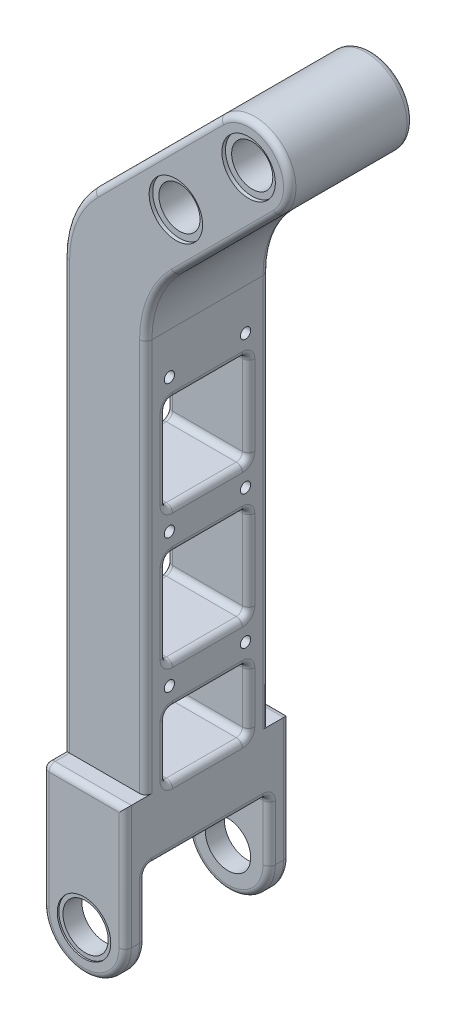
SolidWorks part; units mm, degrees
material "6061 合金"
ref_plane "前视基准面" through (0, 0, 0) normal (0, 0, 1) x (1, 0, 0)
ref_plane "上视基准面" through (0, 0, 0) normal (0, 1, 0) x (1, 0, 0)
ref_plane "右视基准面" through (0, 0, 0) normal (1, 0, 0) x (0, 0, -1)
other "Configuration Table"
sketch "草图1" plane through (0, 0, 0) normal (0, 0, 1) x (1, 0, 0)
  circle A0 centre (0, 0) radius 20
  circle A1 centre (0, 0) radius 10
  dimension "D1" = 40
  dimension "D2" = 20
extrude "凸台-拉伸1" add sketch "草图1" along normal blind 60 contours A1 | A0 region at (0, 0, 0)
ref_plane "基准面1" through (0, 0, 30) normal (0, 0, 1) x (1, 0, 0)
sketch "草图2" plane through (0, 0, 30) normal (0, 0, 1) x (1, 0, 0)
  line L0 (0, 0) -> (-70, -70) construction
  line L1 (-70, -70) -> (-70, -320) construction
  line L2 (0, -57.3148) -> (0, 49.9409) construction
  line L3 (-56.8582, 0) -> (46.4003, 0) construction
  line L4 (-14.1421, 14.1421) -> (-90, -61.7157)
  line L5 (14.1421, -14.1421) -> (-50, -78.2843)
  line L6 (-90, -61.7157) -> (-90, -320)
  line L7 (-50, -78.2843) -> (-50, -320)
  line L8 (-90, -320) -> (-50, -320)
  circle A2 centre (0, 0) radius 20 construction
  arc A3 (-14.1421, 14.1421) -> (14.1421, -14.1421) centre (0, 0) ccw
  dimension "D1" = 45
  dimension "D2" = 250
  dimension "D3" = 70
  dimension "D4" = 40
  dimension "D5" = 40
extrude "凸台-拉伸2" add sketch "草图2" along normal mid plane 60 contours L7 L8 L6 L4 A3 L5
sketch "草图4" plane through (0, 0, 60) normal (0, 0, 1) x (1, 0, 0)
  line L0 (-90, -61.7157) -> (-90, -320) construction
  line L1 (-90, -290) -> (-50, -290)
  line L2 (-90, -290) -> (-90, -350)
  line L4 (-50, -290) -> (-50, -350)
  line L5 (-50, -78.2843) -> (-50, -320) construction
  line L6 (-90, -320) -> (-50, -320) construction
  arc A0 (-90, -350) -> (-50, -350) centre (-70, -350) ccw
  circle A1 centre (-70, -350) radius 11
  dimension "D3" = 22
  dimension "D1" = 30
  dimension "D2" = 30
extrude "凸台-拉伸3" add sketch "草图4" along normal blind 10
mirror "镜向1" about plane through (0, 0, 30) normal (0, 0, 1) of "凸台-拉伸3"
sketch "草图5" plane through (0, 0, 0) normal (0, 1, 0) x (1, 0, 0)
  line L0 (0, 0) -> (0, -78.0582) construction
ref_plane "基准面2" through (-70, 0, 0) normal (-1, 0, 0) x (0, 0, 1)
sketch "草图7" plane through (-70, 0, 0) normal (-1, 0, 0) x (0, 0, 1)
  line L0 (-34.1239, -350) -> (109.535, -350) construction
sketch "草图8" plane through (0, 0, 60) normal (0, 0, 1) x (1, 0, 0)
  line L0 (0, 0) -> (-70, -70) construction
  circle A0 centre (-35.3553, -35.3553) radius 10
  dimension "D1" = 20
  dimension "D2" = 50
extrude "切除-拉伸1" cut sketch "草图8" against normal blind 100
fillet "圆角1" radius 50 2 edges at (-90, -61.7157, 30) (-50, -78.2843, 30)
fillet "圆角2" radius 3 34 edges at (-50, -320, 70) (-70, -370, 70) (-50, -335, 60) (-70, -370, 60) (-50, -335, 0) (-70, -370, 0) (-50, -320, -10) (-70, -370, -10) (-70, -320, 60) (-50, -320, 30) (-70, -320, 0) (-90, -290, 65) (-90, -320, 70) (-90, -335, 60) (-90, -320, 30) (-90, -335, 0) (-90, -320, -10) (-90, -290, -5) (-50, -194.4975, 0) (-46.194, -79.8608, 0) (-10.6066, -38.8909, 0) (14.1421, 14.1421, 0) (-44.7487, -16.4645, 0) (-86.194, -63.2922, 0) (-90, -186.2132, 0) (14.1421, 14.1421, 60) (-10.6066, -38.8909, 60) (-46.194, -79.8608, 60) (-50, -194.4975, 60) (-90, -186.2132, 60) (-86.194, -63.2922, 60) (-44.7487, -16.4645, 60) (-70, -290, 70) (-70, -290, -10)
sketch "草图9" plane through (0, 0, 70) normal (0, 0, 1) x (1, 0, 0)
  circle A0 centre (-70, -350) radius 13
  dimension "D1" = 26
extrude "切除-拉伸2" cut sketch "草图9" against normal blind 0.75
sketch "草图10" plane through (0, 0, -10) normal (0, 0, -1) x (-1, 0, 0)
  circle A0 centre (70, -350) radius 13
  dimension "D1" = 26
extrude "切除-拉伸3" cut sketch "草图10" against normal blind 0.75 contours A0
sketch "草图11" plane through (-90, 0, 0) normal (-1, 0, 0) x (0, 0, 1)
  circle A0 centre (48.5, -118.9949) radius 2.5
  circle A1 centre (48.5, -183.9949) radius 2.5
  circle A2 centre (48.5, -248.9949) radius 2.5
  circle A3 centre (11.5, -248.9949) radius 2.5
  circle A4 centre (11.5, -183.9949) radius 2.5
  circle A5 centre (11.5, -118.9949) radius 2.5
  dimension "D1" = 5
extrude "切除-拉伸4" cut sketch "草图11" against normal through all contours A1 | A2 | A0 | A3 | A4 | A5 region at (-90, -183.9949, 48.5) region at (-90, -248.9949, 48.5)
sketch "草图12" plane through (-90, 0, 0) normal (-1, 0, 0) x (0, 0, 1)
  line L0 (30, -62.0134) -> (30, -339.6946) construction
  line L1 (10, -128.9949) -> (50, -128.9949)
  line L2 (10, -128.9949) -> (10, -173.9949)
  line L3 (10, -173.9949) -> (50, -173.9949)
  line L4 (50, -128.9949) -> (50, -173.9949)
  line L5 (10, -193.9949) -> (50, -193.9949)
  line L6 (10, -193.9949) -> (10, -238.9949)
  line L7 (10, -238.9949) -> (50, -238.9949)
  line L8 (50, -193.9949) -> (50, -238.9949)
  line L9 (10, -258.9949) -> (50, -258.9949)
  line L10 (10, -258.9949) -> (10, -290)
  line L11 (10, -290) -> (50, -290)
  line L12 (50, -258.9949) -> (50, -290)
  line L13 (19.5, -173.9949) -> (40.5, -173.9949)
  line L14 (19.5, -173.9949) -> (19.5, -193.9949)
  line L15 (19.5, -193.9949) -> (40.5, -193.9949)
  line L16 (40.5, -173.9949) -> (40.5, -193.9949)
  line L17 (19.5, -238.9949) -> (40.5, -238.9949)
  line L18 (19.5, -238.9949) -> (19.5, -258.9949)
  line L19 (19.5, -258.9949) -> (40.5, -258.9949)
  line L20 (40.5, -238.9949) -> (40.5, -258.9949)
  line L21 (60, -82.4264) -> (60, -290) construction
  line L22 (0, -290) -> (0, -82.4264) construction
  line L23 (57, -320) -> (3, -320) construction
  circle A0 centre (48.5, -118.9949) radius 2.5 construction
  circle A1 centre (48.5, -183.9949) radius 2.5 construction
  circle A2 centre (48.5, -248.9949) radius 2.5 construction
  dimension "D1" = 10
  dimension "D2" = 10
  dimension "D3" = 10
  dimension "D4" = 8
  dimension "D5" = 10
  dimension "D6" = 10
  dimension "D7" = 10
  dimension "D8" = 30
extrude "减重" cut sketch "草图12" against normal through all contours L0 L1 L2 L3 | L15 L0 L17 L7 L8 L5 | L0 L5 L6 L7 | L19 L0 L11 L12 L9 | L0 L9 L10 L11 | L1 L0 L13 L3 L4 region at (-90, -151.4949, 40) region at (-90, -151.4949, 20) region at (-90, -216.4949, 40) region at (-90, -216.4949, 20) region at (-90, -274.4975, 40) region at (-90, -274.4975, 20)
fillet "圆角3" radius 3 36 edges at (-90, -258.9949, 30) (-50, -258.9949, 30) (-50, -290, 30) (-90, -290, 30) (-50, -238.9949, 30) (-50, -193.9949, 30) (-90, -193.9949, 30) (-90, -238.9949, 30) (-50, -173.9949, 30) (-90, -173.9949, 30) (-50, -128.9949, 30) (-90, -128.9949, 30) (-70, -290, 10) (-90, -274.4975, 10) (-70, -258.9949, 10) (-50, -274.4975, 10) (-50, -274.4975, 50) (-70, -258.9949, 50) (-90, -274.4975, 50) (-70, -290, 50) (-50, -216.4949, 50) (-70, -193.9949, 50) (-90, -216.4949, 50) (-70, -238.9949, 50) (-70, -238.9949, 10) (-90, -216.4949, 10) (-70, -193.9949, 10) (-50, -216.4949, 10) (-70, -173.9949, 10) (-90, -151.4949, 10) (-70, -128.9949, 10) (-50, -151.4949, 10) (-50, -151.4949, 50) (-70, -128.9949, 50) (-90, -151.4949, 50) (-70, -173.9949, 50)
sketch "草图13" plane through (0, 0, 60) normal (0, 0, 1) x (1, 0, 0)
  circle A0 centre (0, 0) radius 13
  circle A1 centre (-35.3553, -35.3553) radius 13
  dimension "D1" = 26
  dimension "D2" = 26
extrude "切除-拉伸6" cut sketch "草图13" against normal blind 1.75
sketch "草图14" plane through (0, 0, 0) normal (0, 0, -1) x (-1, 0, 0)
  circle A0 centre (0, 0) radius 13
  circle A1 centre (35.3553, -35.3553) radius 13
  dimension "D1" = 26
  dimension "D2" = 26
extrude "切除-拉伸7" cut sketch "草图14" against normal blind 1.75
